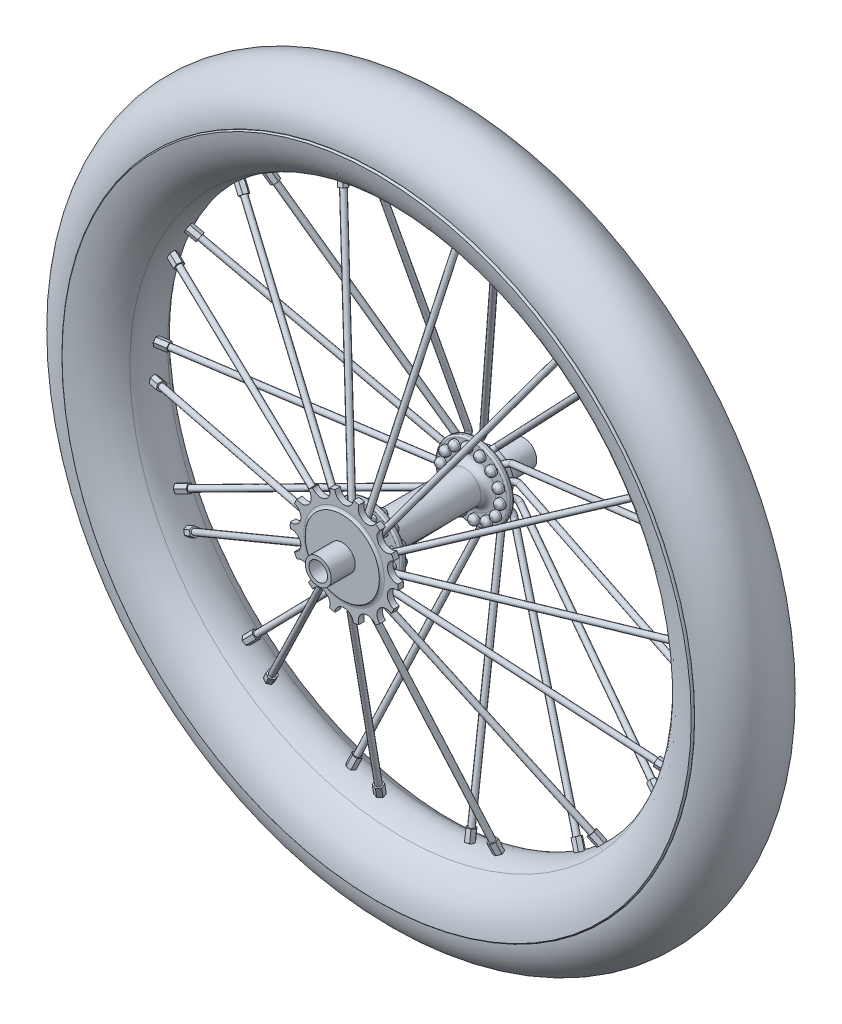
SolidWorks part; units mm, degrees
ref_plane "Front Plane" through (0, 0, 0) normal (0, 0, 1) x (1, 0, 0)
ref_plane "Top Plane" through (0, 0, 0) normal (0, 1, 0) x (1, 0, 0)
ref_plane "Right Plane" through (0, 0, 0) normal (1, 0, 0) x (0, 0, -1)
sketch "Sketch1" plane through (0, 0, 0) normal (1, 0, 0) x (0, 0, -1)
  line L0 (0, 0) -> (-165, 0) construction
  line L1 (0, 145.26) -> (0, 0) construction
  line L2 (0, 145.26) -> (0, 170.26) construction
  arc A0 (-22.5, 170.26) -> (22.5, 170.26) centre (0, 170.26) cw
  arc A1 (-22.5, 170.26) -> (-23.9433, 169.8454) centre (-23.0393, 169.4179) ccw
  arc A2 (22.5, 170.26) -> (23.9433, 169.8454) centre (23.0393, 169.4179) cw
  spline S0 degree 3 poles (-23.9433, 169.8454) (-22.6201, 160.0541) (-18.8848, 152.5655) (-10.1919, 146.9845) knots 0 0 0 0 1 1 1 1
  spline S1 degree 3 poles (23.9433, 169.8454) (22.6201, 160.0541) (18.8848, 152.5655) (10.1919, 146.9845) knots 0 0 0 0 1 1 1 1
  spline S2 degree 3 poles (-10.1919, 146.9845) (-7.7428, 145.4122) (0.1938, 143.7322) (7.3553, 145.1634) (10.1919, 146.9845) knots 0 0 0 0 0.5 1 1 1 1
  dimension "D4" = 22.5
  dimension "D5" = 1
  dimension "D1" = 145.26
  dimension "D2" = 165
  dimension "D3" = 25
  dimension "D6" = 0.75
revolve "Revolve2" add sketch "Sketch1" angle 360 about L0
sketch "Sketch3" plane through (0, 0, 0) normal (0, 0, 1) x (1, 0, 0)
  circle A0 centre (0, 0) radius 5
  circle A1 centre (0, 0) radius 8.8
  dimension "D1" = 10
  dimension "D2" = 17.6
extrude "Boss-Extrude1" add sketch "Sketch3" along normal blind 38.5 and the other way blind 38.5 separate body
sketch "Sketch4" plane through (0, 0, 38.5) normal (0, 0, 1) x (1, 0, 0)
  arc A0 (-4.9815, 28.6603) -> (-7.9471, 27.9834) centre (0, 0) ccw
  arc A1 (-4.9815, 28.6603) -> (4.9815, 28.6603) centre (0, 29.09) ccw
  arc A2 (7.9471, 27.9834) -> (16.9234, 23.6606) centre (12.6217, 26.2092) ccw
  arc A3 (19.3016, 21.7641) -> (25.5134, 13.9747) centre (22.7435, 18.1373) ccw
  arc A4 (26.8332, 11.2341) -> (29.0502, 1.5209) centre (28.3607, 6.4731) ccw
  arc A5 (29.0502, -1.5209) -> (26.8332, -11.2341) centre (28.3607, -6.4731) ccw
  arc A6 (25.5134, -13.9747) -> (19.3016, -21.7641) centre (22.7435, -18.1373) ccw
  arc A7 (16.9234, -23.6606) -> (7.9471, -27.9834) centre (12.6217, -26.2092) ccw
  arc A8 (4.9815, -28.6603) -> (-4.9815, -28.6603) centre (0, -29.09) ccw
  arc A9 (-7.9471, -27.9834) -> (-16.9234, -23.6606) centre (-12.6217, -26.2092) ccw
  arc A10 (-19.3016, -21.7641) -> (-25.5134, -13.9747) centre (-22.7435, -18.1373) ccw
  arc A11 (-26.8332, -11.2341) -> (-29.0502, -1.5209) centre (-28.3607, -6.4731) ccw
  arc A12 (-29.0502, 1.5209) -> (-26.8332, 11.2341) centre (-28.3607, 6.4731) ccw
  arc A13 (-25.5134, 13.9747) -> (-19.3016, 21.7641) centre (-22.7435, 18.1373) ccw
  arc A14 (-16.9234, 23.6606) -> (-7.9471, 27.9834) centre (-12.6217, 26.2092) ccw
  arc A15 (-16.9234, 23.6606) -> (-19.3016, 21.7641) centre (0, 0) ccw
  arc A16 (-25.5134, 13.9747) -> (-26.8332, 11.2341) centre (0, 0) ccw
  arc A17 (-29.0502, 1.5209) -> (-29.0502, -1.5209) centre (0, 0) ccw
  arc A18 (-26.8332, -11.2341) -> (-25.5134, -13.9747) centre (0, 0) ccw
  arc A19 (-19.3016, -21.7641) -> (-16.9234, -23.6606) centre (0, 0) ccw
  arc A20 (-7.9471, -27.9834) -> (-4.9815, -28.6603) centre (0, 0) ccw
  arc A21 (4.9815, -28.6603) -> (7.9471, -27.9834) centre (0, 0) ccw
  arc A22 (16.9234, -23.6606) -> (19.3016, -21.7641) centre (0, 0) ccw
  arc A23 (25.5134, -13.9747) -> (26.8332, -11.2341) centre (0, 0) ccw
  arc A24 (29.0502, -1.5209) -> (29.0502, 1.5209) centre (0, 0) ccw
  arc A25 (26.8332, 11.2341) -> (25.5134, 13.9747) centre (0, 0) ccw
  arc A26 (19.3016, 21.7641) -> (16.9234, 23.6606) centre (0, 0) ccw
  arc A27 (7.9471, 27.9834) -> (4.9815, 28.6603) centre (0, 0) ccw
  circle A28 centre (0, 0) radius 4.9815
  point P47 (0, 0)
  dimension "D1" = 58.18
  dimension "D2" = 10
  dimension "D3" = 14
extrude "Boss-Extrude2" add sketch "Sketch4" along normal blind 4
sketch "Sketch5" plane through (0, 0, 38.5) normal (0, 0, -1) x (-1, 0, 0)
  circle A0 centre (0, 0) radius 11.5
  circle A1 centre (0, 0) radius 5 construction
  circle A2 centre (0, 0) radius 5
  dimension "D1" = 23
extrude "Boss-Extrude3" add sketch "Sketch5" along normal blind 4 separate body
sketch "Sketch6" plane through (0, 0, 34.5) normal (0, 0, -1) x (-1, 0, 0)
  circle A0 centre (0, 0) radius 10
  circle A1 centre (0, 0) radius 5 construction
  circle A2 centre (0, 0) radius 5
  dimension "D1" = 20
extrude "Boss-Extrude4" add sketch "Sketch6" along normal blind 4 separate body
mirror "Mirror2" about plane through (0, 0, 0) normal (0, 0, 1) of bodies 106 105
fillet "Fillet4" radius 2 1 edges at (-11.5, 0, 34.5)
fillet "Fillet5" radius 2 1 edges at (-11.5, 0, -34.5)
sketch "Sketch7" plane through (0, 0, 0) normal (0, 1, 0) x (1, 0, 0)
  line L0 (0, 34.334) -> (0, 23.9782) construction
  line L1 (-20, 30.5) -> (-5, 30.5)
  line L2 (-20, 30.5) -> (-20, 27.5)
  line L3 (-20, 27.5) -> (-5, 27.5)
  line L4 (-5, 30.5) -> (-5, 27.5)
  line L5 (-10, 30.5) -> (10, 30.5) construction
  line L6 (0, 0) -> (78.8131, 0) construction
  line L7 (-5, -30.5) -> (-5, -27.5)
  line L8 (-20, -30.5) -> (-5, -30.5)
  line L9 (-20, -30.5) -> (-20, -27.5)
  line L10 (-20, -27.5) -> (-5, -27.5)
  line L11 (0, 65.1398) -> (0, -65.3757) construction
  dimension "D1" = 3
  dimension "D2" = 20
  dimension "D3" = 5
revolve "Revolve3" add sketch "Sketch7" angle 360 about L11
fillet "Fillet6" radius 4 2 edges at (8.8, 0, -27.5) (-8.8, 0, 27.5)
fillet "Fillet7" radius 1 4 edges at (-20, 0, 27.5) (-20, 0, 30.5) (-20, 0, -30.5) (-20, 0, -27.5)
sketch "Sketch8" plane through (0, 0, 42.5) normal (0, 0, 1) x (1, 0, 0)
  circle A0 centre (0, 0) radius 5
  circle A1 centre (0, 0) radius 7
  dimension "D1" = 10
  dimension "D2" = 14
extrude "Boss-Extrude5" add sketch "Sketch8" along normal blind 2
sketch3d "3DSketch3"
  line L0 (-15.945, 1.6501, -27.5) -> (-15.945, 1.6501, -31.6073)
  line L1 (-19.163, 3.6032, -34.5083) -> (-126.9665, 69.032, -1.2854)
  line L2 (-15.945, 1.6501, -27.5) -> (-15.945, 1.6501, -24.5)
  arc A0 (-15.945, 1.6501, -31.6073) -> (-19.163, 3.6032, -34.5083) centre (-18.5096, 3.2066, -31.6073) ccw
  point P0 (-15.945, 1.6501, -27.5)
  point P1 (-126.9665, 69.032, -1.2854)
  point P8 (-15.945, 1.6501, -35.5)
  point P9 (-16.9531, 5.7712, -31.6073)
  dimension "D3" = 3
  dimension "D1" = 8
  dimension "D2" = 3
ref_plane "Plane3" through (-126.9665, 69.032, -1.2854) normal (-0.8267, 0.5017, 0.2548) x (0.2178, -0.1322, 0.967)
sketch "Sketch9" plane through (0, 0, -38.5) normal (0, 0, -1) x (-1, 0, 0)
  circle A0 centre (0, 0) radius 7
  circle A1 centre (0, 0) radius 5
  dimension "D1" = 14
extrude "Boss-Extrude8" add sketch "Sketch9" along normal blind 4
sketch "Sketch18" plane through (-126.9665, 69.032, -1.2854) normal (-0.8267, 0.5017, 0.2548) x (0.2178, -0.1322, 0.967)
  circle A0 centre (0, 0) radius 1.5
sweep "Sweep3" add profiles "Sketch18" path "3DSketch3"
sketch "Sketch20" plane through (-126.9665, 69.032, -1.2854) normal (-0.8267, 0.5017, 0.2548) x (0.2178, -0.1322, 0.967)
  line L1 (-2.2299, -0.775) -> (-0.4438, -2.3187)
  line L2 (-0.4438, -2.3187) -> (1.7862, -1.5436)
  line L3 (1.7862, -1.5436) -> (2.2299, 0.775)
  line L4 (2.2299, 0.775) -> (0.4438, 2.3187)
  line L5 (0.4438, 2.3187) -> (-1.7862, 1.5436)
  line L6 (-1.7862, 1.5436) -> (-2.2299, -0.775)
  circle A0 centre (0, 0) radius 2.0445 construction
extrude "Boss-Extrude14" add sketch "Sketch20" against normal blind 6
sketch "Sketch21" plane through (0, 0, -24.5) normal (0, 0, 1) x (1, 0, 0)
  circle A0 centre (-15.945, 1.6501) radius 2.5
  dimension "D1" = 5
extrude "Boss-Extrude15" add sketch "Sketch21" against normal up to next
fillet "Fillet12" radius 2 1 edges at (-13.445, 1.6501, -24.5)
pattern_circular "CirPattern3" count 14 over 360 about axis through (0, 0, -38.5) along (0, 0, 1) of "Boss-Extrude15", "Fillet12", "Boss-Extrude14", "Sweep3"
sketch3d "3DSketch4"
  line L0 (8.4049, -13.5283, 27.5) -> (8.4049, -13.5283, 31.5629)
  line L1 (11.04, -16.2606, 34.4554) -> (97.8854, -106.3096, 0.0294)
  line L2 (8.4049, -13.5283, 27.5) -> (8.4049, -13.5283, 24.5)
  arc A0 (8.4049, -13.5283, 31.5629) -> (11.04, -16.2606, 34.4554) centre (10.4874, -15.6876, 31.5629) ccw
  point P0 (97.8854, -106.3096, 0.0294)
  point P1 (8.4049, -13.5283, 27.5)
  point P7 (8.4049, -13.5283, 35.5)
  point P8 (12.6468, -13.6051, 31.5629)
  dimension "D2" = 3
  dimension "D1" = 8
  dimension "D3" = 3
ref_plane "Plane4" through (97.8854, -106.3096, 0.0294) normal (0.6693, -0.694, -0.2653) x (-0.743, -0.6252, -0.239)
sketch "Sketch22" plane through (97.8854, -106.3096, 0.0294) normal (0.6693, -0.694, -0.2653) x (-0.743, -0.6252, -0.239)
  circle A0 centre (0, 0) radius 1.5
  dimension "D1" = 3
sweep "Sweep4" add profiles "Sketch22" path "3DSketch4"
sketch "Sketch23" plane through (0, 0, 24.5) normal (0, 0, -1) x (-1, 0, 0)
  circle A0 centre (-8.4049, -13.5283) radius 2.5
  dimension "D1" = 5
extrude "Boss-Extrude16" add sketch "Sketch23" against normal up to next
fillet "Fillet13" radius 2 1 edges at (5.9049, -13.5283, 24.5)
sketch "Sketch24" plane through (97.8854, -106.3096, 0.0294) normal (0.6693, -0.694, -0.2653) x (-0.743, -0.6252, -0.239)
  line L1 (1.2053, 2.1028) -> (-1.2184, 2.0952)
  line L2 (-1.2184, 2.0952) -> (-2.4237, -0.0076)
  line L3 (-2.4237, -0.0076) -> (-1.2053, -2.1028)
  line L4 (-1.2053, -2.1028) -> (1.2184, -2.0952)
  line L5 (1.2184, -2.0952) -> (2.4237, 0.0076)
  line L6 (2.4237, 0.0076) -> (1.2053, 2.1028)
  circle A0 centre (0, 0) radius 2.099 construction
extrude "Boss-Extrude17" add sketch "Sketch24" against normal blind 6
pattern_circular "CirPattern9" count 14 over 360 about axis through (0, 0, -38.5) along (0, 0, 1) of "Boss-Extrude17", "Fillet13", "Boss-Extrude16", "Sweep4" reverse direction yes
sketch "Sketch25" plane through (0, 0, 42.5) normal (0, 0, 1) x (1, 0, 0)
  circle A0 centre (0, 0) radius 20
  circle A1 centre (0, 0) radius 32.9357
  dimension "D1" = 40
extrude "Cut-Extrude1" cut sketch "Sketch25" against normal blind 1
fillet "Fillet15" radius 2 1 edges at (20, 0, 41.5)
sketch "Sketch26" plane through (0, 0, -42.5) normal (0, 0, -1) x (-1, 0, 0)
  circle A0 centre (0, 0) radius 5 construction
  circle A1 centre (0, 0) radius 7
  circle A2 centre (0, 0) radius 7
  circle A3 centre (0, 0) radius 5
  dimension "D1" = 0
extrude "Boss-Extrude18" add sketch "Sketch26" along normal blind 13
sketch "Sketch27" plane through (0, 0, 44.5) normal (0, 0, 1) x (1, 0, 0)
  circle A0 centre (0, 0) radius 5 construction
  circle A1 centre (0, 0) radius 7
  circle A2 centre (0, 0) radius 7
  circle A3 centre (0, 0) radius 5
  dimension "D1" = 0
extrude "Boss-Extrude19" add sketch "Sketch27" along normal blind 10.98
